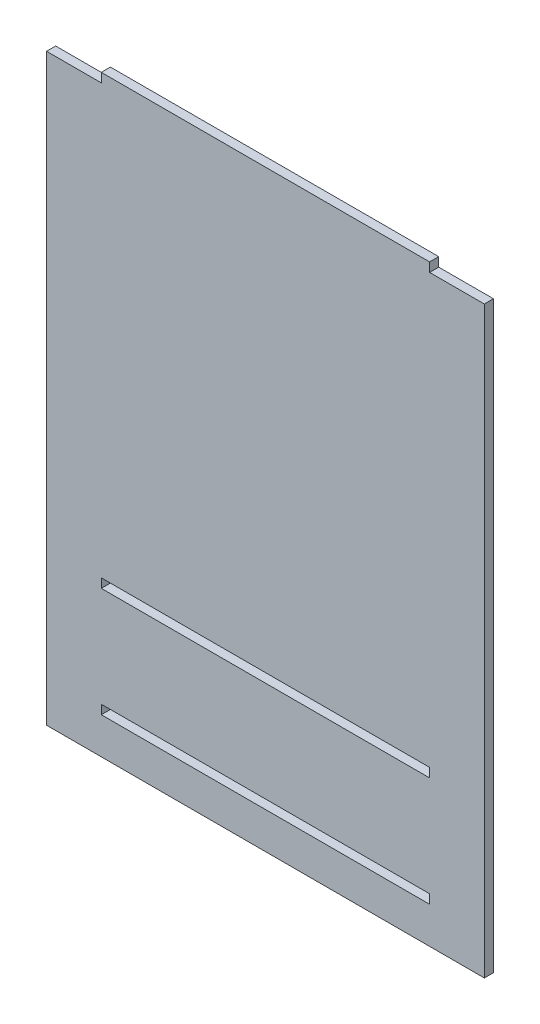
SolidWorks part; units mm, degrees
ref_plane "Front" through (0, 0, 0) normal (0, 0, 1) x (1, 0, 0)
ref_plane "Top" through (0, 0, 0) normal (0, 1, 0) x (1, 0, 0)
ref_plane "Right" through (0, 0, 0) normal (1, 0, 0) x (0, 0, -1)
sketch "Sketch2" plane through (0, 0, 0) normal (0, 0, 1) x (1, 0, 0)
  line L0 (133.35, 0) -> (152.4, 0)
  line L1 (0, 0) -> (19.05, 0)
  line L2 (0, 0) -> (0, 203.2)
  line L3 (0, 203.2) -> (19.05, 203.2)
  line L4 (152.4, 0) -> (152.4, 203.2)
  line L9 (19.05, 0) -> (133.35, 0)
  line L10 (19.05, 15.875) -> (133.35, 15.875)
  line L11 (19.05, 15.875) -> (19.05, 12.7)
  line L12 (19.05, 12.7) -> (133.35, 12.7)
  line L13 (133.35, 15.875) -> (133.35, 12.7)
  line L15 (19.05, 203.2) -> (19.05, 206.375)
  line L16 (19.05, 206.375) -> (133.35, 206.375)
  line L17 (133.35, 203.2) -> (133.35, 206.375)
  line L18 (133.35, 203.2) -> (152.4, 203.2)
  line L20 (19.05, 53.975) -> (133.35, 53.975)
  line L21 (19.05, 53.975) -> (19.05, 50.8)
  line L22 (19.05, 50.8) -> (133.35, 50.8)
  line L23 (133.35, 53.975) -> (133.35, 50.8)
  dimension "D1" = 152.4
  dimension "D2" = 203.2
  dimension "D3" = 12.7
  dimension "D4" = 3.175
  dimension "D5" = 114.3
  dimension "D6" = 19.05
  dimension "D7" = 114.3
  dimension "D8" = 19.05
  dimension "D9" = 3.175
  dimension "D10" = 3.175
  dimension "D11" = 114.3
  dimension "D12" = 19.05
  dimension "D13" = 50.8
extrude "Boss-Extrude1" add sketch "Sketch2" along normal blind 3.175
